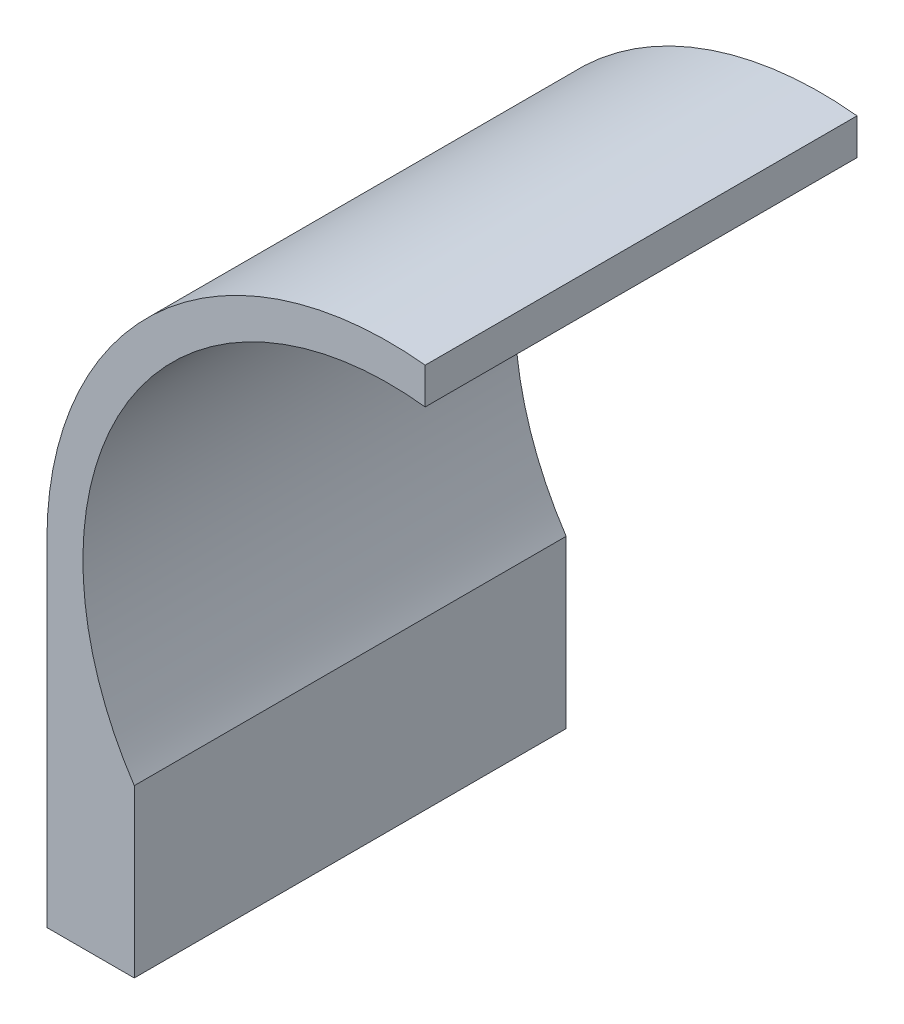
SolidWorks part; units mm, degrees
ref_plane "Front Plane" through (0, 0, 0) normal (0, 0, 1) x (1, 0, 0)
ref_plane "Top Plane" through (0, 0, 0) normal (0, 1, 0) x (1, 0, 0)
ref_plane "Right Plane" through (0, 0, 0) normal (1, 0, 0) x (0, 0, -1)
sketch "Sketch1" plane through (0, 0, 0) normal (0, 0, 1) x (1, 0, 0)
  line L0 (0, 0) -> (0, -136.3227) construction
  line L1 (-70.7312, -47.1391) -> (70.7312, -47.1391) construction
  line L2 (0, 0) -> (101.5936, 0) construction
  line L3 (10.1, 111.7322) -> (10.1, -25.0367) construction
  line L4 (-70.7312, -47.1391) -> (-70.7312, -63.42)
  line L5 (10.1, 94.4616) -> (10.1, 84.3978)
  line L6 (-70.7312, -63.42) -> (-70.7312, -93.42)
  line L7 (0, 0) -> (-138.7196, 0) construction
  line L8 (-95, 0) -> (-95, -93.42)
  line L9 (-70.7312, -93.42) -> (-95, -93.42)
  circle A0 centre (0, 0) radius 85 construction
  circle A1 centre (0, 0) radius 95 construction
  arc A2 (-70.7312, -47.1391) -> (10.1, 84.3978) centre (0, 0) cw
  arc A3 (-95, 0) -> (10.1, 94.4616) centre (0, 0) cw
  dimension "D1" = 170
  dimension "D2" = 190
  dimension "D6" = 95
  dimension "D3" = 167.1
  dimension "D4" = 10.1
  dimension "D5" = 30
extrude "Inner Ring - Left Side" add sketch "Sketch1" along normal blind 120
